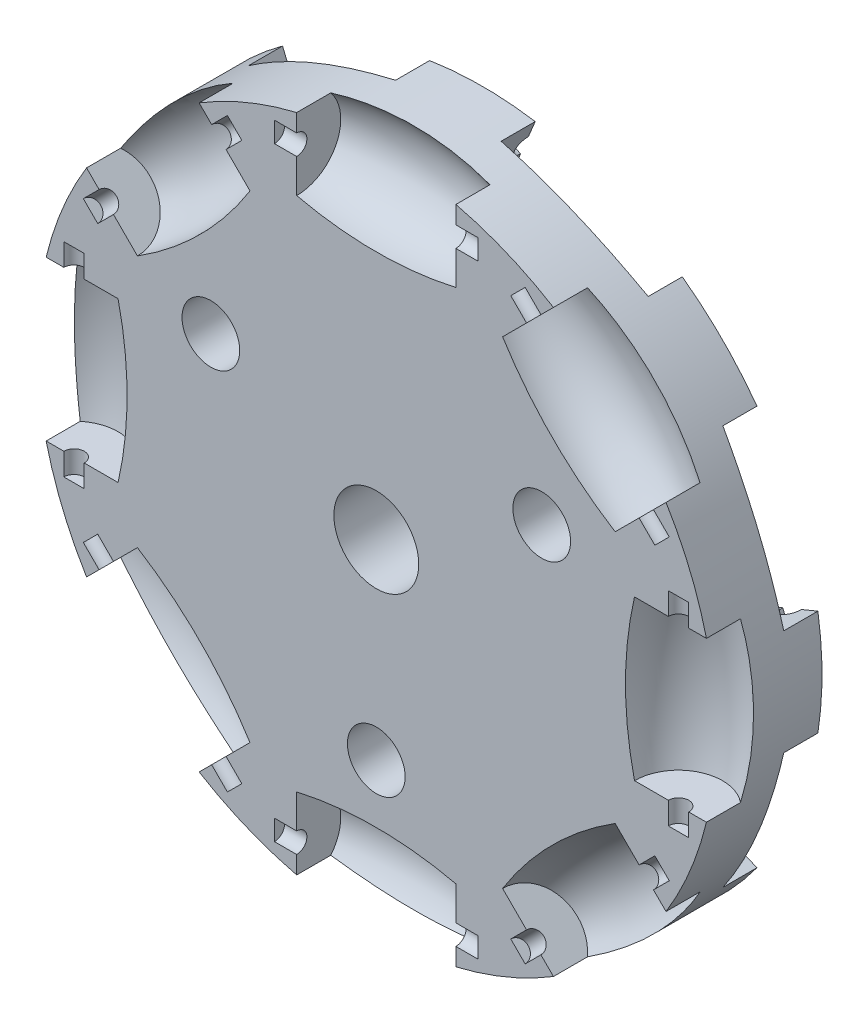
SolidWorks part; units mm, degrees
ref_plane "Front Plane" through (0, 0, 0) normal (0, 0, 1) x (1, 0, 0)
ref_plane "Top Plane" through (0, 0, 0) normal (0, 1, 0) x (1, 0, 0)
ref_plane "Right Plane" through (0, 0, 0) normal (1, 0, 0) x (0, 0, -1)
sketch "Sketch1" plane through (0, 0, 0) normal (0, 0, 1) x (1, 0, 0)
  circle A0 centre (0, 0) radius 25.4
  point P6 (-12.0183, -8.0692)
  point P7 (-18.8859, -8.736)
  point P11 (0, 0)
  point P12 (0, 0)
  dimension "D1" = 50.8
extrude "Boss-Extrude1" add sketch "Sketch1" along normal mid plane 7.9375
ref_plane "Plane1" through (0, 0, 3.9688) normal (0, 0, 1) x (1, 0, 0)
ref_plane "Plane2" through (0, 0, -3.9688) normal (0, 0, 1) x (1, 0, 0)
sketch "Sketch5" plane through (0, 0, 3.9688) normal (0, 0, 1) x (1, 0, 0)
  line L0 (-5.9531, 25.8994) -> (-5.9531, 22.606)
  line L1 (-5.9531, 22.606) -> (5.9531, 22.606)
  line L2 (5.9531, 22.606) -> (5.9531, 25.8994)
  line L3 (-5.9531, 22.606) -> (-8.0326, 22.606) construction
  arc A2 (-5.9531, 25.8994) -> (5.9531, 25.8994) centre (0, 0) cw
  point P2 (0, 26.5748)
  point P7 (0, 22.606)
  dimension "D1" = 11.9062
  dimension "D2" = 7.9375
  dimension "D3" = 22.606
revolve "Cut-Revolve5" cut sketch "Sketch5" angle 360 about L1
sketch "Sketch8" plane through (0, 0, -3.9688) normal (0, 0, 1) x (1, 0, 0)
  line L0 (4.4113, 26.2061) -> (3.151, 23.1634)
  line L1 (3.151, 23.1634) -> (14.1509, 18.6071)
  line L2 (14.1509, 18.6071) -> (15.4112, 21.6497)
  line L3 (3.151, 23.1634) -> (-2.0499, 25.3177) construction
  line L4 (0, 0) -> (9.7202, 23.4665) construction
  line L5 (0, 0) -> (0, 7.8748) construction
  arc A0 (4.4113, 26.2061) -> (15.4112, 21.6497) centre (0, 0) cw
  arc A2 (-5.9531, 24.6925) -> (5.9531, 24.6925) centre (0, 0) ccw construction
  point P2 (4.4312, 26.254)
  point P6 (8.6509, 20.8852)
  point P11 (9.7202, 23.4665)
  point P14 (10.1697, 24.5519)
  point P16 (15.5027, 21.8705)
  dimension "D1" = 11.9062
  dimension "D2" = 7.9375
  dimension "D3" = 22.5
  dimension "D4" = 22.606
revolve "Cut-Revolve6" cut sketch "Sketch8" angle 360 about L3
sketch "Sketch6" plane through (0, 0, 0) normal (1, 0, 0) x (0, 0, -1)
  arc A0 (-3.9688, 19.3126) -> (-1.4207, 24.6925) centre (-3.9688, 22.606) ccw construction
  circle A1 centre (-3.9688, 22.606) radius 0.762
  point P4 (-3.9688, 22.606)
  dimension "D1" = 1.524
extrude "Cut-Extrude2" cut sketch "Sketch6" against normal mid plane 15.24
ref_axis "Axis1" through (0, 0, -8.8615) along (0, 0, 1)
ref_plane "Plane3" through (0, 0, 0) normal (0.9239, -0.3827, 0) x (0, 0, -1)
sketch "Sketch10" plane through (0, 0, 0) normal (0.9239, -0.3827, 0) x (0, 0, -1)
  arc A1 (1.4207, 24.6925) -> (3.9688, 19.3126) centre (3.9688, 22.606) ccw construction
  circle A2 centre (3.9688, 22.606) radius 0.762
  point P4 (3.9688, 22.606)
  dimension "D1" = 1.524
extrude "Cut-Extrude3" cut sketch "Sketch10" against normal mid plane 15.24
pattern_circular "CirPattern1" count 8 over 360 about axis through (0, 0, 3.9688) along (0, 0, -1) of "Cut-Revolve5", "Cut-Revolve6", "Cut-Extrude2", "Cut-Extrude3"
sketch "Sketch16" plane through (0, 0, 3.9688) normal (0, 0, 1) x (1, 0, 0)
  circle A0 centre (0, -14.2875) radius 2.159
  circle A1 centre (-12.3733, 7.1437) radius 2.159
  circle A2 centre (12.3733, 7.1438) radius 2.159
  point P4 (-33.4047, 7.5099)
  point P5 (0, 0)
  point P9 (0, 0)
  dimension "D1" = 4.318
  dimension "D2" = 14.2875
  dimension "D3" = 3
extrude "Cut-Extrude7" cut sketch "Sketch16" against normal through all
sketch "Sketch17" plane through (0, 0, 3.9688) normal (0, 0, 1) x (1, 0, 0)
  circle A0 centre (0, 0) radius 3.175
  dimension "D1" = 6.35
extrude "Cut-Extrude8" cut sketch "Sketch17" against normal through all
